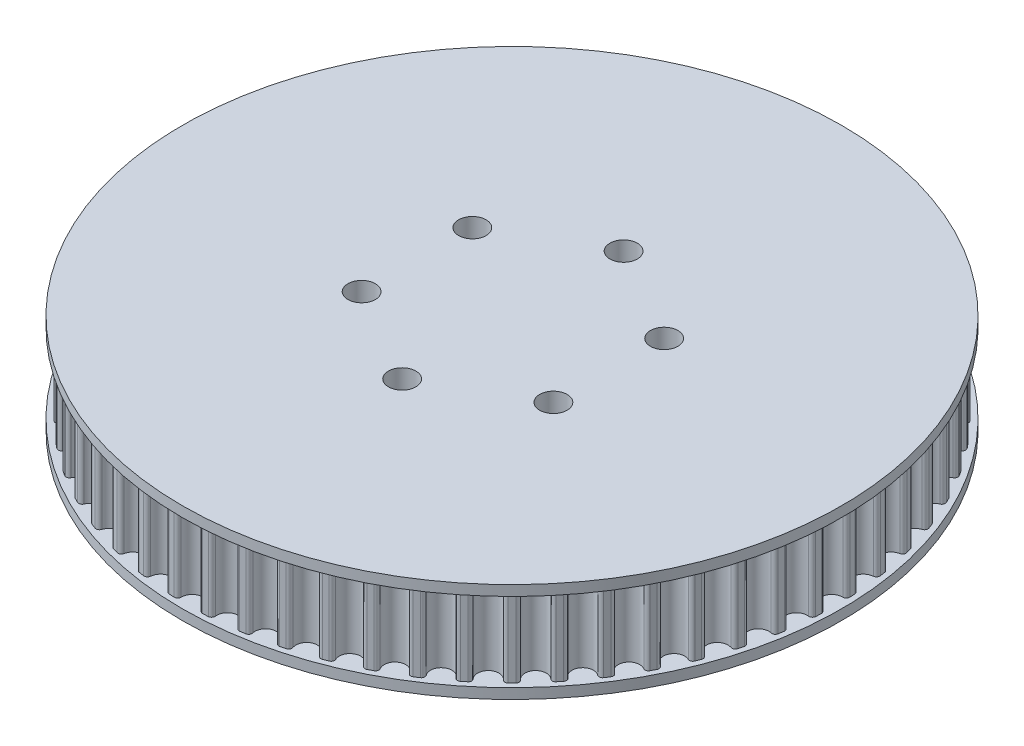
SolidWorks part; units mm, degrees
ref_plane "前视基准面" through (0, 0, 0) normal (0, 0, 1) x (1, 0, 0)
ref_plane "上视基准面" through (0, 0, 0) normal (0, 1, 0) x (1, 0, 0)
ref_plane "右视基准面" through (0, 0, 0) normal (1, 0, 0) x (0, 0, -1)
other "Configuration Table"
sketch "草图1" plane through (0, 0, 0) normal (0, 1, 0) x (1, 0, 0)
  circle A1 centre (0, 0) radius 47.175
  dimension "D2" = 94.35
extrude "凸台-拉伸1" add sketch "草图1" along normal blind 11.5
sketch "草图2" plane through (0, 11.5, 0) normal (0, 1, 0) x (1, 0, 0)
  line L0 (0, 0) -> (0, 47.745) construction
  line L1 (0, 47.745) -> (0, 47.175)
  line L2 (0, 47.175) -> (0, 45.015)
  line L3 (-1.625, 47.175) -> (1.625, 47.175)
  line L4 (-1.56, 46.575) -> (-1.6999, 47.7147)
  line L5 (1.56, 46.575) -> (1.6999, 47.7147)
  circle A0 centre (0, 0) radius 47.745 construction
  circle A1 centre (0, 46.575) radius 1.56
  point P11 (0, 47.175)
  point P15 (0, 45.795)
  point P17 (0, 46.575)
  circle M9 centre (0, 0) radius 47.175
  dimension "D1" = 95.49
  dimension "D4" = 3.12
  dimension "D2" = 0.57
  dimension "D3" = 2.16
  dimension "D5" = 3.25
  dimension "D6" = 7
  dimension "D7" = 7
  dimension "D8" = 1.56
extrude "切除-拉伸1" cut sketch "草图2" against normal through all contours A1 L2 M9 | A1 L2 M9
fillet "圆角1" radius 0.5 2 edges at (1.4491, 5.75, -47.1527) (-1.4491, 5.75, -47.1527)
pattern_circular "阵列(圆周)1" count 60 over 360 about axis through (0, 0, 0) along (0, 1, 0) of "圆角1", "切除-拉伸1"
sketch "草图5" plane through (0, 0, 0) normal (0, -1, 0) x (1, 0, 0)
  circle A0 centre (0, 0) radius 48
  dimension "D1" = 96
extrude "凸台-拉伸2" add sketch "草图5" along normal blind 1.5
sketch "草图6" plane through (0, -1.5, 0) normal (0, -1, 0) x (1, 0, 0)
  circle A0 centre (0, 0) radius 32.6
  dimension "D1" = 65.2
extrude "切除-拉伸4" cut sketch "草图6" against normal blind 8.7
sketch "草图7" plane through (0, -1.5, 0) normal (0, -1, 0) x (1, 0, 0)
  circle A0 centre (0, 0) radius 34.1
  dimension "D1" = 68.2
extrude "切除-拉伸5" cut sketch "草图7" against normal blind 1.7
sketch "草图8" plane through (0, 11.5, 0) normal (0, 1, 0) x (1, 0, 0)
  circle A0 centre (0, 0) radius 48
extrude "凸台-拉伸3" add sketch "草图8" along normal blind 1.5
sketch "草图9" plane through (0, 7.2, 0) normal (0, -1, 0) x (1, 0, 0)
  circle A0 centre (0, 0) radius 22.5
  dimension "D1" = 45
extrude "切除-拉伸7" cut sketch "草图9" against normal blind 2
sketch "草图10" plane through (0, 9.2, 0) normal (0, -1, 0) x (1, 0, 0)
  circle A0 centre (0, 0) radius 16
  circle A1 centre (0, 16) radius 2
  circle A2 centre (-16, 0) radius 2
  circle A3 centre (0, -16) radius 2
  circle A4 centre (16, 0) radius 2
  dimension "D1" = 32
  dimension "D2" = 4
  dimension "D3" = 4
  dimension "D4" = 4
  dimension "D5" = 4
extrude "切除-拉伸8" cut sketch "草图10" against normal through all contours A0 A1 | A0 A1
pattern_circular "阵列(圆周)2" count 6 over 360 about axis through (0, 0, -0.1274) along (0, 1, 0) of "切除-拉伸8"
